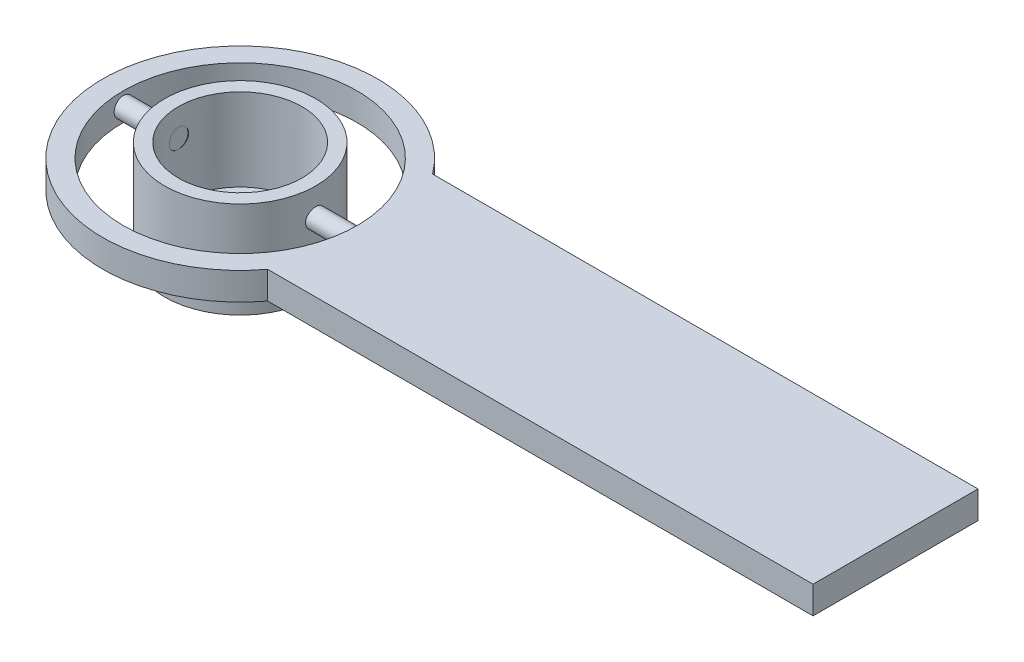
SolidWorks part; units mm, degrees
note: The reader was unsure of these and kept them because the rebuilt part matched: shared geometry of "Sketch1<4>".
ref_plane "Front Plane" through (0, 0, 0) normal (0, 0, 1) x (1, 0, 0)
ref_plane "Top Plane" through (0, 0, 0) normal (0, 1, 0) x (1, 0, 0)
ref_plane "Right Plane" through (0, 0, 0) normal (1, 0, 0) x (0, 0, -1)
sketch "Sketch1" plane through (0, 0, 0) normal (0, 1, 0) x (1, 0, 0)
  line L0 (0, 0) -> (238.3831, 0) construction
  line L1 (40, -30) -> (238.3831, -30)
  line L2 (40, 30) -> (238.3831, 30)
  line L4 (238.3831, -30) -> (238.3831, 30)
  line L5 (0, 30) -> (238.3831, 30) construction
  line L6 (0, -30) -> (238.3831, -30) construction
  circle A0 centre (0, 0) radius 22.5
  circle A1 centre (0, 0) radius 42.5
  circle A2 centre (0, 0) radius 50
  dimension "D3" = 45
  dimension "D4" = 85
  dimension "D5" = 100
  dimension "D1" = 30
  dimension "D2" = 30
extrude "Extrude-Thin1" add sketch "Sketch1" along normal blind 10 and the other way blind 25 thin contours A0 | L1 L4 L2
sketch "Sketch3" plane through (0, -25, 0) normal (0, -1, 0) x (1, 0, 0)
  circle A0 centre (0, 0) radius 22.5
  circle A1 centre (0, 0) radius 27.5
  circle M1 centre (0, 0) radius 22.5
extrude "Boss-Extrude1" add sketch "Sketch3" against normal blind 5 contours M1
extrude "Boss-Extrude2" add sketch "Sketch1<4>" along normal blind 5 and the other way blind 5 contours A2 A1 | A2 L1 L4 L2
sketch "Sketch1<4>" plane through (0, 0, 0) normal (0, 1, 0) x (1, 0, 0) same geometry as "Sketch1"
ref_plane "Plane2" through (0, 0, 0) normal (1, 0, 0) x (0, 0, -1)
sketch "Sketch4" plane through (0, 0, 0) normal (1, 0, 0) x (0, 0, -1)
  circle A0 centre (0, 0) radius 3.5
ref_plane "Plane3" through (27.5, 0, 0) normal (1, 0, 0) x (0, 0, -1)
sketch "Sketch5" plane through (27.5, 0, 0) normal (1, 0, 0) x (0, 0, -1)
  circle A0 centre (0, 0) radius 3.5
extrude "Cut-Extrude1" cut sketch "Sketch5" against normal up to surface (5.2739 mm away)
mirror "Mirror1" about plane through (0, 0, 0) normal (1, 0, 0) of "Cut-Extrude1"
ref_plane "Plane4" through (42.5, 0, 0) normal (-1, 0, 0) x (0, 0, 1)
sketch "Sketch6" plane through (42.5, 0, 0) normal (-1, 0, 0) x (0, 0, 1)
  circle A0 centre (0, 0) radius 3.5
extrude "Boss-Extrude3" add sketch "Sketch6" along normal up to surface (20.2739 mm away) contours A0
ref_plane "Plane5" through (-42.5, 0, 0) normal (1, 0, 0) x (0, 0, -1)
sketch "Sketch7" plane through (-42.5, 0, 0) normal (1, 0, 0) x (0, 0, -1)
  circle A0 centre (0, 0) radius 3.5
ref_plane "Plane6" through (-22.5, 0, 0) normal (1, 0, 0) x (0, 0, -1)
extrude "Boss-Extrude5" add sketch "Sketch7" along normal up to surface (20 mm away)
